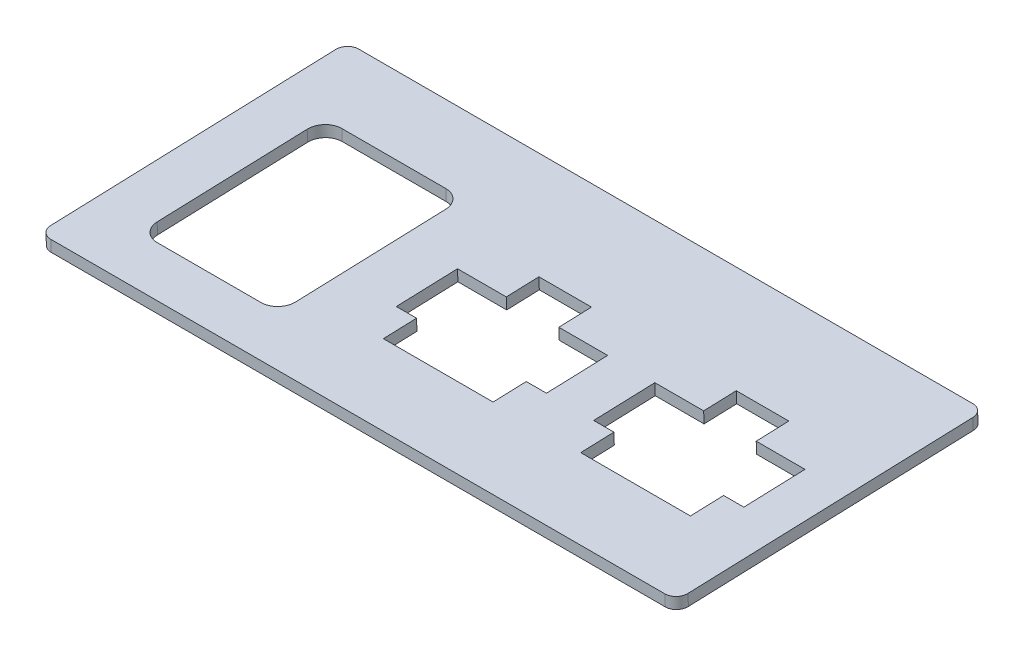
SolidWorks part; units mm, degrees
ref_plane "Front Plane" through (0, 0, 0) normal (0, 0, 1) x (1, 0, 0)
ref_plane "Top Plane" through (0, 0, 0) normal (0, 1, 0) x (1, 0, 0)
ref_plane "Right Plane" through (0, 0, 0) normal (1, 0, 0) x (0, 0, -1)
sketch "Sketch1" plane through (0, -69.2407, -2.4179) normal (0, 0.9994, 0.0349) x (1, 0, 0)
  line L1 (-52.175, -2.8069) -> (-56.175, -2.8069) construction
  line L2 (55.275, 49.051) -> (-55.275, 49.051) construction
  line L8 (-55.175, -4.3069) -> (55.175, -4.3069)
  line L9 (55.175, -4.3069) -> (55.175, 49.051)
  line L10 (55.175, 49.051) -> (-55.175, 49.051)
  line L11 (-55.175, 49.051) -> (-55.175, -4.3069)
  dimension "D1" = 1.5
  dimension "D2" = 3
  dimension "D5" = 3
extrude "Boss-Extrude1" add sketch "Sketch1" along normal blind 2
sketch "Sketch2" plane through (0, -69.2407, -2.4179) normal (0, -0.9994, -0.0349) x (1, 0, 0)
  line L0 (-4.05, -25.4722) -> (-4.05, -31.1222)
  line L1 (-43.175, -4.1222) -> (-25.175, -4.1222)
  line L2 (-46.175, -7.1222) -> (-46.175, -33.1222)
  line L3 (-43.175, -36.1222) -> (-25.175, -36.1222)
  line L4 (-22.175, -7.1222) -> (-22.175, -33.1222)
  line L5 (-12.5, -14.8722) -> (-9, -14.8722)
  line L6 (-12.5, -14.8722) -> (-12.5, -25.4722)
  line L7 (-12.5, -25.4722) -> (-4.05, -25.4722)
  line L8 (13.5, -14.8722) -> (13.5, -25.4722)
  line L9 (-9, -9.1222) -> (10, -9.1222)
  line L10 (-9, -9.1222) -> (-9, -14.8722)
  line L11 (-4.05, -31.1222) -> (5.05, -31.1222)
  line L12 (10, -9.1222) -> (10, -14.8722)
  line L13 (10, -14.8722) -> (13.5, -14.8722)
  line L14 (5.05, -25.4722) -> (5.05, -31.1222)
  line L15 (5.05, -25.4722) -> (13.5, -25.4722)
  line L16 (-13, -6.6222) -> (14, -33.6222) construction
  line L17 (-13, -6.6222) -> (14, -6.6222) construction
  line L18 (-13, -6.6222) -> (-13, -33.6222) construction
  line L19 (-13, -33.6222) -> (14, -33.6222) construction
  line L20 (14, -6.6222) -> (14, -33.6222) construction
  line L21 (17.5875, 3.7502) -> (17.5875, -36.664) construction
  line L22 (47.675, -20.1722) -> (21.675, -20.1722) construction
  line L23 (34.675, -9.1222) -> (34.675, -31.1222) construction
  line L24 (21.175, -6.6222) -> (21.175, -33.6222) construction
  line L25 (48.175, -33.6222) -> (21.175, -33.6222) construction
  line L26 (48.175, -6.6222) -> (48.175, -33.6222) construction
  line L27 (48.175, -6.6222) -> (21.175, -6.6222) construction
  line L28 (-48.175, -20.1222) -> (-46.175, -20.1222) construction
  line L29 (-48.175, -2.1222) -> (-20.175, -2.1222) construction
  line L30 (-48.175, -2.1222) -> (-48.175, -38.1222) construction
  line L31 (-48.175, -38.1222) -> (-20.175, -38.1222) construction
  line L32 (-20.175, -2.1222) -> (-20.175, -38.1222) construction
  line L33 (-34.175, -4.1222) -> (-34.175, -2.1222) construction
  line L34 (0.5, -9.1222) -> (0.5, -31.1222) construction
  line L35 (-12.5, -20.1722) -> (13.5, -20.1722) construction
  line L36 (48.175, -6.6222) -> (21.175, -33.6222) construction
  line L37 (30.125, -25.4722) -> (21.675, -25.4722)
  line L38 (30.125, -25.4722) -> (30.125, -31.1222)
  line L39 (25.175, -14.8722) -> (21.675, -14.8722)
  line L40 (25.175, -9.1222) -> (25.175, -14.8722)
  line L41 (39.225, -31.1222) -> (30.125, -31.1222)
  line L42 (44.175, -9.1222) -> (44.175, -14.8722)
  line L43 (44.175, -9.1222) -> (25.175, -9.1222)
  line L44 (21.675, -14.8722) -> (21.675, -25.4722)
  line L45 (47.675, -25.4722) -> (39.225, -25.4722)
  line L46 (47.675, -14.8722) -> (47.675, -25.4722)
  line L47 (47.675, -14.8722) -> (44.175, -14.8722)
  line L48 (39.225, -25.4722) -> (39.225, -31.1222)
  line L49 (21.175, -20.1222) -> (14, -20.1222) construction
  line L50 (-55.175, 4.3069) -> (55.175, 4.3069) construction
  line L51 (48.175, -20.1222) -> (52.175, -20.1222) construction
  line L52 (55.175, 4.3069) -> (55.175, -49.051) construction
  line L53 (-46.6585, -44.5513) -> (46.6585, -44.5513) construction
  line L54 (-13, -20.1222) -> (-20.175, -20.1222) construction
  line L55 (-34.175, -2.1222) -> (-34.175, 4.3069) construction
  line L56 (-34.175, -38.1222) -> (-34.175, -44.5513) construction
  line L57 (-55.175, -49.051) -> (-55.175, 4.3069) construction
  line L58 (-48.175, -20.1222) -> (-52.175, -20.1222) construction
  arc A0 (-46.175, -33.1222) -> (-43.175, -36.1222) centre (-43.175, -33.1222) ccw
  arc A1 (-25.175, -36.1222) -> (-22.175, -33.1222) centre (-25.175, -33.1222) ccw
  arc A2 (-25.175, -4.1222) -> (-22.175, -7.1222) centre (-25.175, -7.1222) cw
  arc A3 (-43.175, -4.1222) -> (-46.175, -7.1222) centre (-43.175, -7.1222) ccw
  point P28 (0.5, -20.1222)
  point P63 (34.675, -20.1222)
  dimension "D1" = 3
  dimension "D2" = 32
  dimension "D3" = 24
  dimension "D4" = 28
  dimension "D5" = 36
  dimension "D6" = 26
  dimension "D7" = 22
  dimension "D8" = 10.6
  dimension "D9" = 19
  dimension "D10" = 9.1
  dimension "D11" = 5.75
  dimension "D12" = 27
  dimension "D13" = 27
  dimension "D14" = 4
  dimension "D15" = 3
  dimension "D16" = 3
extrude "Cut-Extrude1" cut sketch "Sketch2" against normal up to next
fillet "Fillet1" radius 2 4 edges at (-55.175, -68.3916, 1.9212) (55.175, -68.3916, 1.9212) (55.175, -66.5294, -51.4042) (-55.175, -66.5294, -51.4042)
